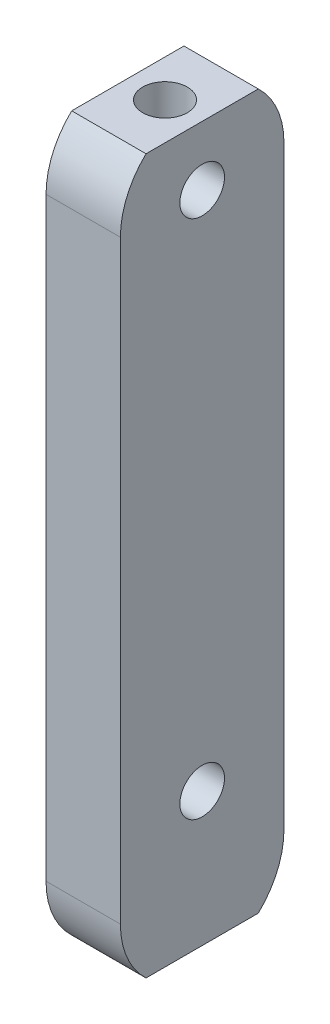
SolidWorks part; units mm, degrees
ref_plane "Front" through (0, 0, 0) normal (0, 0, 1) x (1, 0, 0)
ref_plane "Top" through (0, 0, 0) normal (0, 1, 0) x (1, 0, 0)
ref_plane "Right" through (0, 0, 0) normal (1, 0, 0) x (0, 0, -1)
sketch "Sketch1" plane through (0, 0, 0) normal (1, 0, 0) x (0, 0, -1)
  line L0 (0, 20) -> (0, -20) construction
  line L1 (-5.5, 20) -> (-5.5, -20)
  line L2 (5.5, 20) -> (5.5, -20)
  line L3 (-3.7749, -24) -> (3.7749, -24)
  line L4 (-3.7749, 24) -> (3.7749, 24)
  circle A0 centre (0, 20) radius 1.5
  arc A1 (-5.5, 20) -> (-3.7749, 24) centre (0, 20) cw
  arc A2 (5.5, -20) -> (3.7749, -24) centre (0, -20) cw
  circle A3 centre (0, -15) radius 1.5
  arc A4 (3.7749, 24) -> (5.5, 20) centre (0, 20) cw
  arc A5 (-3.7749, -24) -> (-5.5, -20) centre (0, -20) cw
  point P3 (0, 0)
  point P17 (3.4796, 23.1346)
  dimension "D3" = 4
  dimension "D4" = 3
  dimension "D5" = 4
  dimension "D1" = 35
  dimension "D2" = 40
extrude "Boss-Extrude1" add sketch "Sketch1" along normal blind 5
sketch "Sketch2" plane through (0, -24, 0) normal (0, -1, 0) x (1, 0, 0)
  line L0 (2.5, 3.7749) -> (2.5, -3.7749) construction
  line L1 (5, 3.7749) -> (0, 3.7749) construction
  line L2 (5, -3.7749) -> (0, -3.7749) construction
  circle A0 centre (2.5, 0) radius 1.5
  dimension "D1" = 3
extrude "Cut-Extrude1" cut sketch "Sketch2" against normal blind 5
extrude "Cut-Extrude2" cut sketch "Sketch2<2>" along normal blind 4 from surface starting at face at (2.5, 24, 0)
sketch "Sketch2<2>" plane through (0, -24, 0) normal (0, -1, 0) x (1, 0, 0) same geometry as "Sketch2"
